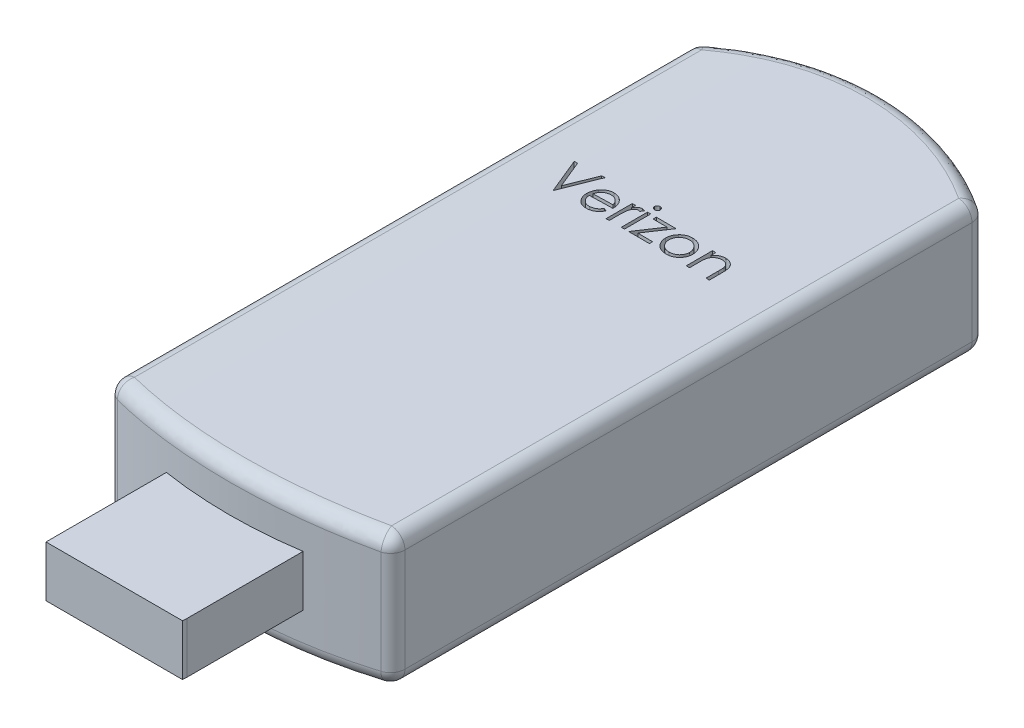
SolidWorks part; units mm, degrees
ref_plane "Front Plane" through (0, 0, 0) normal (0, 0, 1) x (1, 0, 0)
ref_plane "Top Plane" through (0, 0, 0) normal (0, 1, 0) x (1, 0, 0)
ref_plane "Right Plane" through (0, 0, 0) normal (1, 0, 0) x (0, 0, -1)
sketch "Sketch1" plane through (0, 0, 0) normal (0, 1, 0) x (1, 0, 0)
  line L1 (-12.5222, 28.7528) -> (12.5222, 28.7528)
  line L2 (-12.5222, 28.7528) -> (-12.5222, -28.7528)
  line L3 (-12.5222, -28.7528) -> (12.5222, -28.7528)
  line L4 (12.5222, 28.7528) -> (12.5222, -28.7528)
  line L5 (-12.5222, 28.7528) -> (12.5222, -28.7528) construction
  line L6 (-12.5222, -28.7528) -> (12.5222, 28.7528) construction
  point P0 (0, 0)
  dimension "D1" = 57.5056
  dimension "D2" = 25.0444
extrude "Boss-Extrude1" add sketch "Sketch1" along normal mid plane 12.065
sketch "Sketch7" plane through (0, 6.0325, 0) normal (0, 1, 0) x (1, 0, 0)
  text T0 "Verizon"
extrude "Cut-Extrude3" cut sketch "Sketch7" against normal blind 1.524
sketch "Sketch2" plane through (0, 0, 28.7528) normal (0, 0, 1) x (1, 0, 0)
  line L0 (-12.5222, 6.0325) -> (-12.5222, -6.0325) construction
  line L1 (12.5222, 6.0325) -> (12.5222, -6.0325) construction
  line L2 (-12.5222, 6.0325) -> (12.5222, 6.0325) construction
  line L3 (-12.5222, 5.5245) -> (-12.5222, 6.0325)
  line L4 (-12.5222, 6.0325) -> (12.5222, 6.0325)
  line L5 (12.5222, 6.0325) -> (12.5222, 5.5245)
  arc A0 (-12.5222, 5.5245) -> (12.5222, 5.5245) centre (0, -148.5576) cw
  line M2 (12.5222, -6.0325) -> (12.5222, 6.0325)
  line M3 (12.5222, 6.0325) -> (-12.5222, 6.0325)
  line M4 (-12.5222, 6.0325) -> (-12.5222, -6.0325)
  dimension "D1" = 0.508
extrude "Cut-Extrude1" cut sketch "Sketch2" against normal through all contours A0 L4 M4 | A0 M3 M2
sketch "Sketch4" plane through (0, -6.0325, 0) normal (0, -1, 0) x (1, 0, 0)
  line L0 (-12.5222, -28.7528) -> (-12.5222, 28.7528) construction
  line L1 (12.5222, 28.7528) -> (12.5222, -28.7528) construction
  line L2 (12.5222, -28.7528) -> (-12.5222, -28.7528) construction
  line L3 (-12.5222, 28.7528) -> (12.5222, 28.7528) construction
  line L4 (-12.5222, 26.7208) -> (-12.5222, 28.7528)
  line L5 (-12.5222, 28.7528) -> (12.5222, 28.7528)
  line L6 (12.5222, 28.7528) -> (12.5222, 26.7208)
  line L7 (-12.5222, -24.9428) -> (-12.5222, -28.7528)
  line L8 (-12.5222, -28.7528) -> (12.5222, -28.7528)
  line L9 (12.5222, -28.7528) -> (12.5222, -24.9428)
  arc A0 (-12.5222, 26.7208) -> (12.5222, 26.7208) centre (0, -10.8472) cw
  arc A1 (-12.5222, -24.9428) -> (12.5222, -24.9428) centre (0, -6.2697) ccw
  line M1 (12.5222, -28.7528) -> (12.5222, 28.7528)
  line M2 (12.5222, 28.7528) -> (-12.5222, 28.7528)
  line M3 (-12.5222, 28.7528) -> (-12.5222, -28.7528)
  line M4 (-12.5222, -28.7528) -> (12.5222, -28.7528)
  dimension "D1" = 3.81
  dimension "D2" = 2.032
extrude "Cut-Extrude2" cut sketch "Sketch4" against normal through all contours A0 L5 M3 | A0 M2 M1 | A1 M3 M4 | A1 L8 M1
sketch "Sketch5" plane through (0, 0, 0) normal (0, 0, 1) x (1, 0, 0)
  line L1 (-6.0325, 2.2479) -> (6.0325, 2.2479)
  line L2 (-6.0325, 2.2479) -> (-6.0325, -2.2479)
  line L3 (-6.0325, -2.2479) -> (6.0325, -2.2479)
  line L4 (6.0325, 2.2479) -> (6.0325, -2.2479)
  line L5 (-6.0325, 2.2479) -> (6.0325, -2.2479) construction
  line L6 (-6.0325, -2.2479) -> (6.0325, 2.2479) construction
  point P0 (0, 0)
  dimension "D1" = 4.4958
  dimension "D2" = 12.065
extrude "Boss-Extrude2" add sketch "Sketch5" along normal offset from surface (38.5458 mm away) 10.16
sketch "Sketch6" plane through (0, 2.2479, 0) normal (0, 1, 0) x (1, 0, 0)
  line L0 (-6.0325, -38.5458) -> (-6.0325, -38.9128)
  line L1 (-6.0325, -38.9128) -> (6.0172, -38.9128)
  line L2 (6.0172, -38.9128) -> (6.0325, -38.5458)
  line L3 (-6.0325, -38.5458) -> (6.0325, -38.5458)
  arc A0 (-6.0325, -38.5458) -> (6.0325, -38.5458) centre (0, 10.8472) ccw construction
extrude "Boss-Extrude3" add sketch "Sketch6" against normal up to surface (4.4958 mm away) up to face at (0, -2.2479, 33.6255)
fillet "Fillet1" radius 1.27 12 edges at (-12.5222, -0.254, -24.9428) (12.5222, -0.254, -24.9428) (0, -6.0325, -28.7528) (12.5222, -6.0325, 0.889) (12.5222, -0.254, 26.7208) (0, -6.0325, 28.7528) (-12.5222, -6.0325, 0.889) (-12.5222, -0.254, 26.7208) (0, 6.0325, 28.7528) (12.5222, 5.5245, 0.889) (0, 6.0325, -28.7528) (-12.5222, 5.5245, 0.889)
